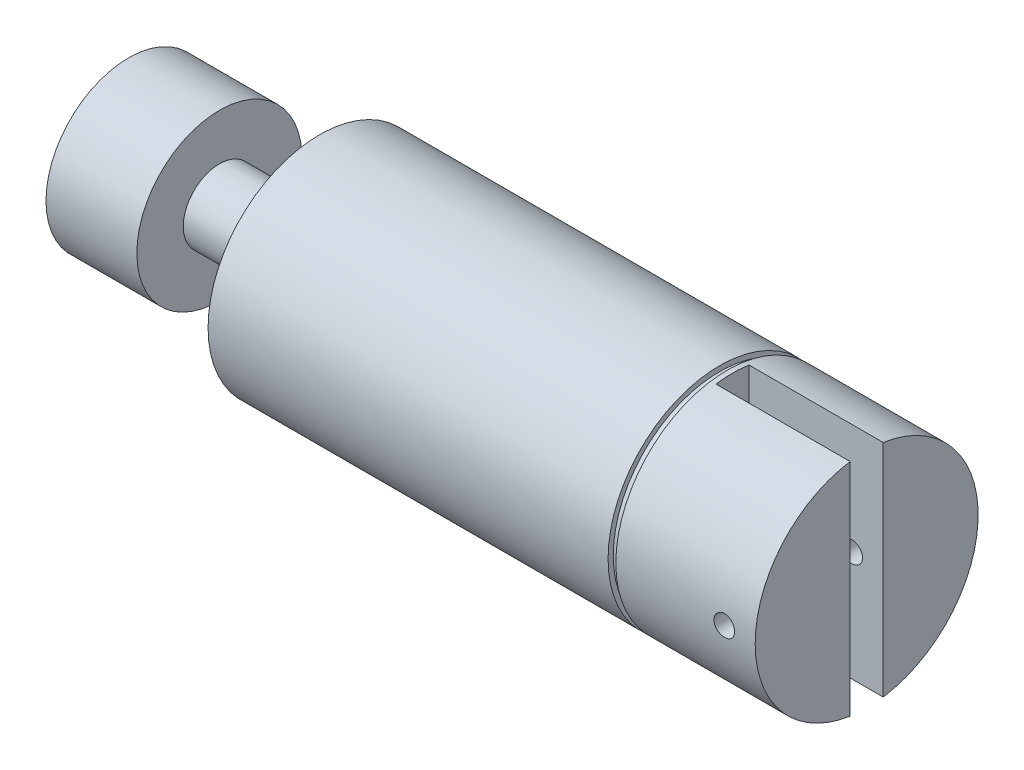
SolidWorks part; units mm, degrees
ref_plane "Front" through (0, 0, 0) normal (0, 0, 1) x (1, 0, 0)
ref_plane "Top" through (0, 0, 0) normal (0, 1, 0) x (1, 0, 0)
ref_plane "Right" through (0, 0, 0) normal (1, 0, 0) x (0, 0, -1)
sketch "Sketch1" plane through (0, 0, 0) normal (0, 0, 1) x (1, 0, 0)
  line L0 (-38.3901, 0) -> (38.3901, 0) construction
  line L1 (-57.25, 0) -> (-57.25, 8)
  line L2 (-57.25, 8) -> (-57.0422, 8)
  line L3 (-57.0422, 8) -> (-48.45, 8)
  line L4 (-48.45, 8) -> (-48.45, 5.8595)
  line L5 (-48.45, 3.5045) -> (-48.45, 5.8595)
  line L6 (-38.75, 3.5045) -> (-38.75, 10.8)
  line L7 (-48.45, 3.5045) -> (-38.75, 3.5045)
  line L8 (-38.75, 10.8) -> (-33.89, 10.8)
  line L9 (14.25, 10.8) -> (0.75, 10.8)
  line L10 (0.75, 10.8) -> (0.75, 10.3)
  line L11 (0.75, 10.3) -> (0, 10.3)
  line L12 (0, 10.3) -> (0, 10.8)
  line L14 (14.25, 10.8) -> (14.25, 0)
  line L15 (14.25, 0) -> (-57.25, 0)
  line L18 (-33.89, 10.8) -> (0, 10.8)
  point P9 (0, 0)
  point P12 (-48.45, 3.5045)
  dimension "D2" = 71.5
  dimension "D3" = 10.8
  dimension "D4" = 8.8
  dimension "D5" = 8
  dimension "D6" = 9.7
  dimension "D14" = 0.75
  dimension "D15" = 0.5
  dimension "D16" = 13.5
revolve "Revolve1" add sketch "Sketch1" angle 360 about L0
sketch "Sketch2" plane through (0, 0, 0) normal (0, 0, 1) x (1, 0, 0)
  line L0 (14.25, -10.8) -> (14.25, 10.8) construction
  circle A0 centre (11.25, 0) radius 1
  dimension "D1" = 2
  dimension "D2" = 3
extrude "Cut-Extrude1" cut sketch "Sketch2" against normal through all both and the other way through all
sketch "Sketch3" plane through (0, 0, 0) normal (0, 1, 0) x (1, 0, 0)
  line L0 (14.25, -10.8) -> (14.25, 10.8) construction
  line L1 (27.25, 1.6) -> (1.25, 1.6)
  line L2 (27.25, 1.6) -> (27.25, -1.6)
  line L3 (27.25, -1.6) -> (1.25, -1.6)
  line L4 (1.25, 1.6) -> (1.25, -1.6)
  line L5 (27.25, 1.6) -> (1.25, -1.6) construction
  line L6 (27.25, -1.6) -> (1.25, 1.6) construction
  line L7 (0.75, 10.3) -> (0.75, -10.3) construction
  point P0 (14.25, 0)
  dimension "D1" = 3.2
  dimension "D2" = 0.5
extrude "Cut-Extrude2" cut sketch "Sketch3" against normal through all both and the other way through all
